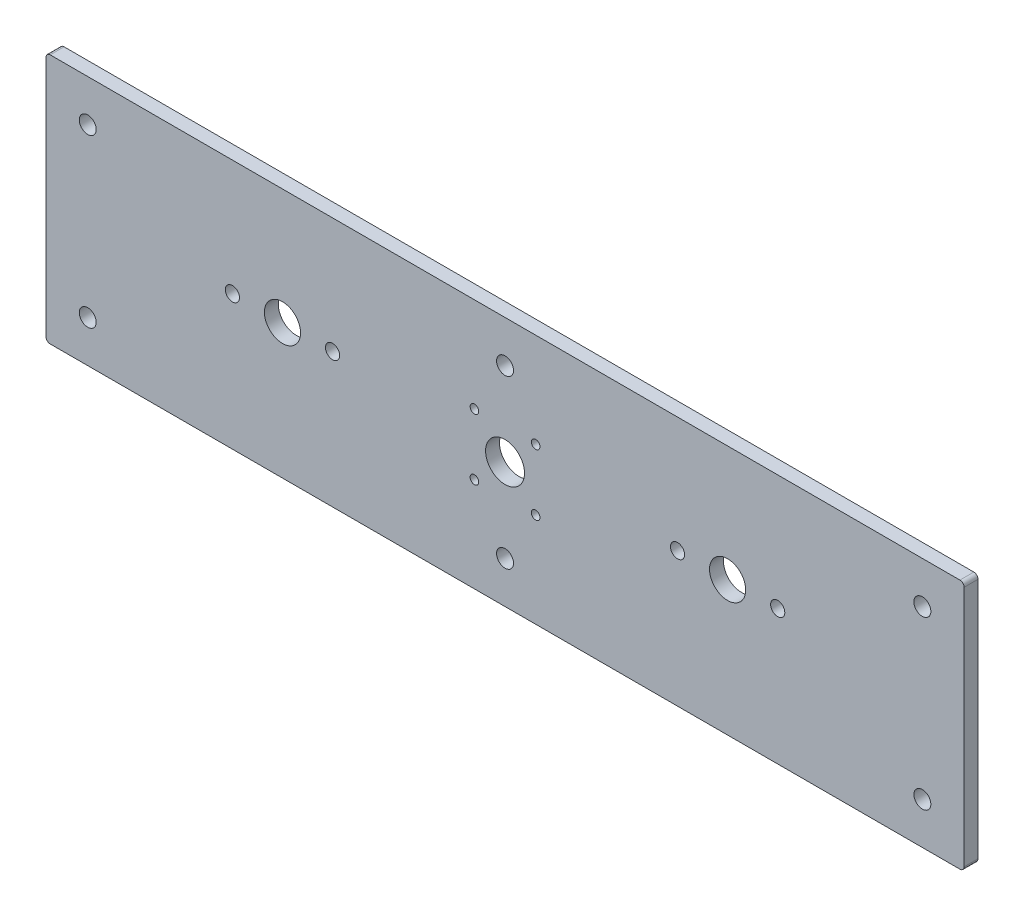
SolidWorks part; units mm, degrees
ref_plane "Front Plane" through (0, 0, 0) normal (0, 0, 1) x (1, 0, 0)
ref_plane "Top Plane" through (0, 0, 0) normal (0, 1, 0) x (1, 0, 0)
ref_plane "Right Plane" through (0, 0, 0) normal (1, 0, 0) x (0, 0, -1)
sketch "Sketch1" plane through (0, 0, 0) normal (0, 0, 1) x (1, 0, 0)
  line L1 (-165, -45) -> (165, -45)
  line L2 (-165, -45) -> (-165, 45)
  line L3 (-165, 45) -> (165, 45)
  line L4 (165, -45) -> (165, 45)
  line L5 (-165, -45) -> (165, 45) construction
  line L6 (-165, 45) -> (165, -45) construction
  point P0 (0, 0)
  dimension "D1" = 330
  dimension "D2" = 90
extrude "Boss-Extrude1" add sketch "Sketch1" along normal mid plane 5
sketch "Sketch2" plane through (0, 0, 2.5) normal (0, 0, 1) x (1, 0, 0)
  line L3 (165, 30) -> (-165, 30)
  line L4 (165, 30) -> (-165, 30) construction
  line L6 (-150, 45) -> (-150, -45)
  line L7 (-150, 45) -> (-150, -45) construction
  line L9 (-165, -30) -> (165, -30)
  line L10 (-165, -30) -> (165, -30) construction
  line L11 (0, 45) -> (0, -45) construction
  line L12 (150, -45) -> (150, 45)
  line L13 (150, -45) -> (150, 45) construction
  line L14 (165, 45) -> (-165, 45) construction
  line L15 (-165, -45) -> (165, -45) construction
  circle A0 centre (150, 30) radius 3.05
  circle A1 centre (150, -30) radius 3.05
  circle A2 centre (0, 30) radius 3.05
  circle A3 centre (0, -30) radius 3.05
  circle A4 centre (-150, -30) radius 3.05
  circle A5 centre (-150, 30) radius 3.05
  dimension "D5" = 6.1
  dimension "D6" = 6.1
  dimension "D7" = 6.1
  dimension "D8" = 6.1
  dimension "D9" = 6.1
  dimension "D10" = 6.1
  dimension "D1" = 15
  dimension "D2" = 15
  dimension "D3" = 15
  dimension "D4" = 15
extrude "Cut-Extrude1" cut sketch "Sketch2" against normal through all
sketch "Sketch3" plane through (0, 0, 2.5) normal (0, 0, 1) x (1, 0, 0)
  line L0 (-165, 3.4) -> (165, 3.4) construction
  circle A0 centre (-80, 3.4) radius 6.5
  circle A1 centre (-62, 3.4) radius 2.55
  circle A2 centre (-98, 3.4) radius 2.55
  dimension "D1" = 13
  dimension "D2" = 5.1
  dimension "D4" = 5.1
  dimension "D7" = 80
  dimension "D3" = 3.4
  dimension "D5" = 18
  dimension "D6" = 18
extrude "Cut-Extrude2" cut sketch "Sketch3" against normal through all
mirror "Mirror1" about plane through (0, 0, 0) normal (1, 0, 0) of "Cut-Extrude2"
sketch "Sketch4" plane through (0, 0, 2.5) normal (0, 0, 1) x (1, 0, 0)
  line L1 (-11, -11) -> (11, -11) construction
  line L2 (-11, -11) -> (-11, 11) construction
  line L3 (-11, 11) -> (11, 11) construction
  line L4 (11, -11) -> (11, 11) construction
  line L5 (-11, -11) -> (11, 11) construction
  line L6 (-11, 11) -> (11, -11) construction
  circle A0 centre (11, 11) radius 1.55
  circle A1 centre (11, -11) radius 1.55
  circle A2 centre (-11, -11) radius 1.55
  circle A3 centre (-11, 11) radius 1.55
  circle A4 centre (0, 0) radius 7
  point P0 (0, 0)
  dimension "D3" = 3.1
  dimension "D4" = 3.1
  dimension "D5" = 3.1
  dimension "D6" = 3.1
  dimension "D7" = 14
  dimension "D1" = 22
  dimension "D2" = 22
extrude "Cut-Extrude3" cut sketch "Sketch4" against normal through all
fillet "Fillet1" radius 1.5 4 edges at (-165, -45, 0) (-165, 45, 0) (165, -45, 0) (165, 45, 0)
equation "\"D8@Sketch2\"=\"D5@Sketch2\""
equation "\"D9@Sketch2\"=\"D5@Sketch2\""
equation "\"D6@Sketch2\"=\"D5@Sketch2\""
equation "\"D7@Sketch2\"=\"D5@Sketch2\""
equation "\"D10@Sketch2\"=\"D5@Sketch2\""
